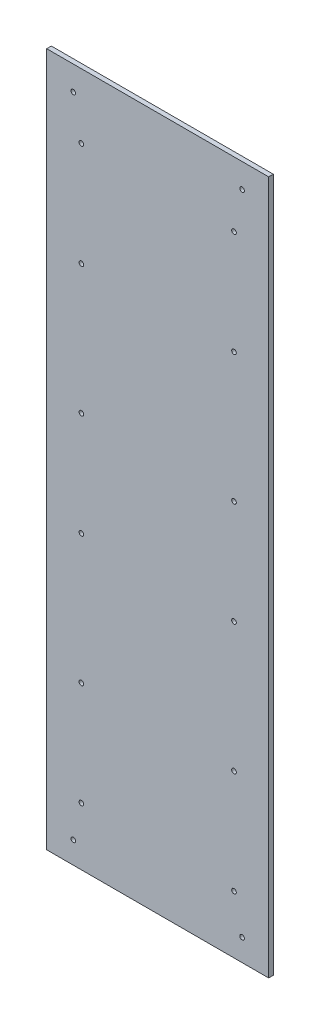
SolidWorks part; units mm, degrees
material "Alumina"
ref_plane "Front Plane" through (0, 0, 0) normal (0, 0, 1) x (1, 0, 0)
ref_plane "Top Plane" through (0, 0, 0) normal (0, 1, 0) x (1, 0, 0)
ref_plane "Right Plane" through (0, 0, 0) normal (1, 0, 0) x (0, 0, -1)
sketch "Sketch1" plane through (0, 0, 0) normal (0, 0, 1) x (1, 0, 0)
  line L1 (48, -150) -> (-48, -150)
  line L2 (48, -150) -> (48, 150)
  line L3 (48, 150) -> (-48, 150)
  line L4 (-48, -150) -> (-48, 150)
  line L5 (48, -150) -> (-48, 150) construction
  line L6 (48, 150) -> (-48, -150) construction
  point P0 (0, 0)
  dimension "D1" = 96
  dimension "D2" = 300
extrude "Boss-Extrude1" add sketch "Sketch1" along normal blind 2
sketch "Sketch2" plane through (0, 0, 2) normal (0, 0, 1) x (1, 0, 0)
  line L0 (-48, 150) -> (-48, -150) construction
  line L1 (48, 150) -> (-48, 150) construction
  line L2 (-48, -150) -> (48, -150) construction
  line L4 (0, -1.1) -> (0, 1.1) construction
  line L5 (-33, 77) -> (-33, -125) construction
  line L6 (33, 77) -> (33, -125) construction
  circle A0 centre (-33, 122) radius 1
  circle A1 centre (-33, 77) radius 1
  circle A9 centre (-33, -125) radius 1
  circle A21 centre (-33, -80) radius 1
  circle A22 centre (-33, -24) radius 1
  circle A23 centre (-33, 21) radius 1
  circle A24 centre (33, 21) radius 1
  circle A25 centre (33, -24) radius 1
  circle A26 centre (33, -80) radius 1
  circle A27 centre (33, -125) radius 1
  circle A28 centre (33, 77) radius 1
  circle A29 centre (33, 122) radius 1
  point P39 (0, 0)
  point P41 (0, 0)
  dimension "D1" = 2
  dimension "D3" = 28
  dimension "D4" = 2
  dimension "D6" = 15
  dimension "D15" = 2
  dimension "D8" = 2
  dimension "D14" = 2
  dimension "D17" = 45
  dimension "D18" = 56
  dimension "D19" = 2
  dimension "D20" = 45
  dimension "D2" = 15
  dimension "D5" = 45
  dimension "D9" = 25
  dimension "D7" = 15
extrude "Cut-Extrude1" cut sketch "Sketch2" against normal blind 10
sketch "Sketch3" plane through (0, 0, 2) normal (0, 0, 1) x (1, 0, 0)
  line L0 (-36.5, 139.5) -> (36.5, 139.5) construction
  line L1 (36.5, 139.5) -> (36.5, -140.5) construction
  line L2 (36.5, -140.5) -> (-36.5, -140.5) construction
  line L3 (-36.5, -140.5) -> (-36.5, 139.5) construction
  line L4 (-48, 150) -> (-48, -150) construction
  line L5 (48, -150) -> (48, 150) construction
  line L6 (48, 150) -> (-48, 150) construction
  line L7 (-48, -150) -> (48, -150) construction
  circle A0 centre (-36.5, 139.5) radius 1
  circle A1 centre (36.5, 139.5) radius 1
  circle A2 centre (-36.5, -140.5) radius 1
  circle A3 centre (36.5, -140.5) radius 1
  dimension "D5" = 2
  dimension "D6" = 2
  dimension "D7" = 2
  dimension "D8" = 2
  dimension "D1" = 11.5
  dimension "D2" = 11.5
  dimension "D3" = 10.5
  dimension "D4" = 9.5
extrude "Cut-Extrude2" cut sketch "Sketch3" against normal blind 10
